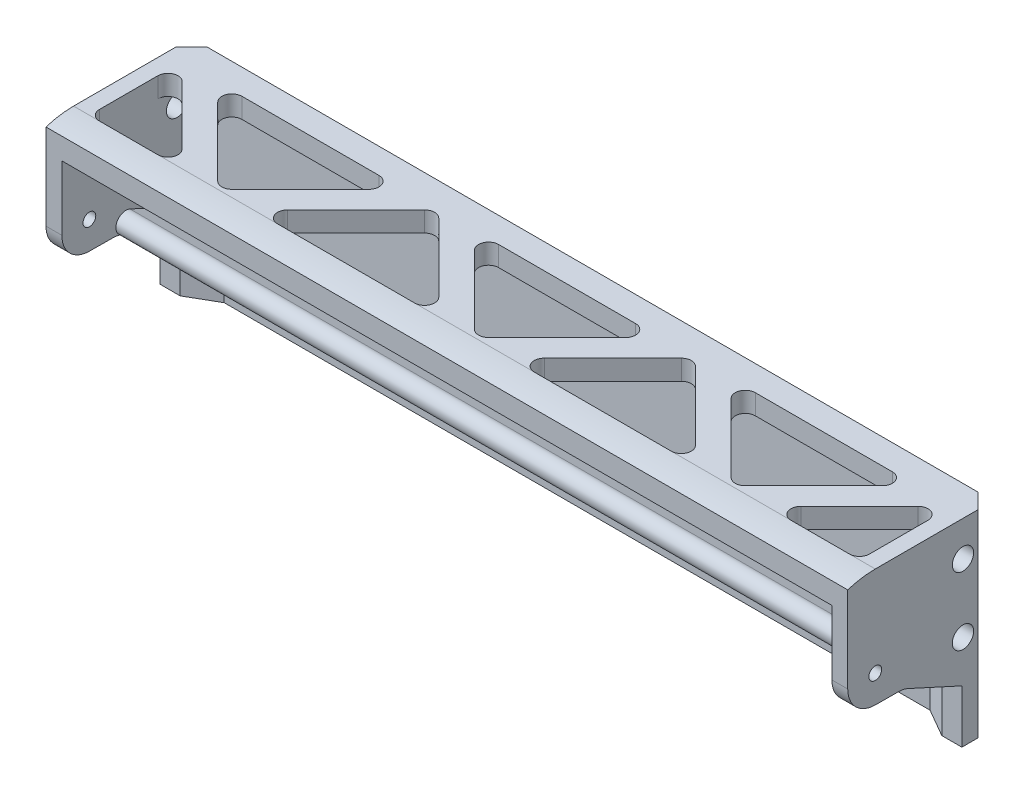
SolidWorks part; units mm, degrees
material "PET"
ref_plane "Front Plane" through (0, 0, 0) normal (0, 0, 1) x (1, 0, 0)
ref_plane "Top Plane" through (0, 0, 0) normal (0, 1, 0) x (1, 0, 0)
ref_plane "Right Plane" through (0, 0, 0) normal (1, 0, 0) x (0, 0, -1)
sketch "Sketch1" plane through (0, 0, 0) normal (1, 0, 0) x (0, 0, -1)
  line L3 (-34.036, 0) -> (42.164, 0) construction
  line L4 (-34.036, 0) -> (-34.036, 28.956) construction
  line L5 (-34.036, 28.956) -> (42.164, 28.956) construction
  line L11 (19.8576, 39.1492) -> (42.164, 28.956)
  line L12 (42.164, 28.956) -> (42.164, 0) construction
  line L13 (42.164, 28.956) -> (42.164, 14.4653)
  line L14 (46.99, 14.4653) -> (46.99, 77.089)
  line L15 (42.164, 14.4653) -> (46.99, 14.4653)
  line L16 (0.889, 48.514) -> (0.889, 75.7224)
  line L17 (9.5529, 39.783) -> (17.2674, 39.7235)
  line L18 (9.6202, 77.089) -> (46.99, 77.089)
  line L20 (37.4015, 44.4881) -> (69.4015, 44.4881) construction
  line L21 (22.4969, 44.9248) -> (42.164, 35.9376) construction
  circle A0 centre (9.6202, 48.514) radius 2.0193
  arc A2 (0.889, 48.514) -> (9.5529, 39.783) centre (9.6202, 48.514) ccw
  circle A7 centre (21.1772, 42.037) radius 3.175 construction
  arc A8 (19.8576, 39.1492) -> (17.2674, 39.7235) centre (17.2184, 33.3737) ccw
  arc A9 (9.6202, 77.089) -> (0.889, 75.7224) centre (9.6202, 48.514) ccw
  circle A12 centre (37.4015, 65.9765) radius 3.3782
  circle A14 centre (37.4015, 44.4881) radius 3.3782
  point P9 (0.889, 48.514)
  dimension "D2" = 4.0386
  dimension "D5" = 0.889
  dimension "D6" = 17.4625
  dimension "D8" = 6.35
  dimension "D13" = 6.35
  dimension "D14" = 28.575
  dimension "D15" = 9.5885
  dimension "D20" = 6.7564
  dimension "D19" = 11.1125
  dimension "D3" = 42.037
  dimension "D4" = 48.514
  dimension "D7" = 11.557
  dimension "D9" = 28.956
  dimension "D10" = 76.2
  dimension "D11" = 41.275
  dimension "D12" = 14.4653
  dimension "D16" = 4.826
  dimension "D17" = 5.7976
  dimension "D18" = 44.4881
  dimension "D21" = 32
  dimension "D22" = 36.5125
  dimension "D23" = 21.4884
extrude "Boss-Extrude1" add sketch "Sketch1" against normal blind 5.017 contours A2 A0 A7 | L13 L15 L14 A2 region at (0, 55.1501, -25.809)
sketch "Sketch2" plane through (0, 0, 0) normal (1, 0, 0) x (0, 0, -1)
  line L0 (22.4969, 44.9248) -> (42.164, 35.9376)
  line L1 (42.164, 35.9376) -> (42.164, 70.739)
  line L2 (42.164, 70.739) -> (40.64, 70.739)
  line L3 (40.64, 70.739) -> (9.6202, 70.739)
  line L4 (46.99, 14.4653) -> (46.99, 77.089)
  line L5 (46.99, 77.089) -> (9.6202, 77.089)
  line L6 (46.99, 14.4653) -> (46.99, 77.089)
  line L7 (46.99, 77.089) -> (9.6202, 77.089)
  line L8 (0.889, 48.514) -> (0.889, 75.7224) construction
  line L9 (0.889, 68.9521) -> (0.889, 75.7224)
  line L10 (46.99, 14.4653) -> (42.164, 14.4653)
  line L11 (42.164, 14.4653) -> (42.164, 28.956)
  line L12 (19.8576, 39.1492) -> (42.164, 28.956)
  line L13 (40.64, 14.4653) -> (40.64, 70.739) construction
  circle A0 centre (21.1772, 42.037) radius 3.175
  arc A1 (9.6202, 70.739) -> (2.8293, 69.6761) centre (9.6202, 48.514) ccw
  arc A2 (9.6202, 77.089) -> (0.889, 75.7224) centre (9.6202, 48.514) ccw
  arc A3 (9.6202, 77.089) -> (0.889, 75.7224) centre (9.6202, 48.514) ccw
  arc A4 (2.8293, 69.6761) -> (0.889, 68.9521) centre (9.6202, 48.514) ccw
  circle A5 centre (21.1772, 42.037) radius 3.175 construction
  line M17 (46.99, 77.089) -> (9.6202, 77.089)
  arc M18 (9.6202, 77.089) -> (0.889, 75.7224) centre (9.6202, 48.514) ccw
  line M19 (0.889, 75.7224) -> (0.889, 48.514)
  line M23 (19.8576, 39.1492) -> (42.164, 28.956)
  line M24 (42.164, 28.956) -> (42.164, 14.4653)
  line M25 (42.164, 14.4653) -> (46.99, 14.4653)
  line M26 (46.99, 14.4653) -> (46.99, 77.089)
  dimension "D1" = 0
  dimension "D2" = 6.35
extrude "Boss-Extrude2" add sketch "Sketch2" along normal blind 121.983 contours A4 A1 L3 M24 M25 M26 M17 M18 M19 | A0 L0 M23 | A0 region at (0, 39.7239, -32.0072) region at (0, 42.037, -21.1772)
sketch "Sketch5" plane through (0, 14.4653, 0) normal (0, -1, 0) x (1, 0, 0)
  line L0 (18.533, -46.99) -> (1.333, -37.0596)
  line L1 (-5.017, -46.99) -> (121.983, -46.99) construction
  line L2 (-5.017, -37.0596) -> (-5.017, -46.99)
  line L3 (-5.017, -46.99) -> (18.533, -46.99)
  line L4 (5.833, -46.99) -> (-5.017, -40.7257)
  line L5 (-5.017, -37.0596) -> (1.333, -37.0596)
  line M6 (121.983, -42.164) -> (-5.017, -42.164)
  dimension "D1" = 30
  dimension "D2" = 23.55
  dimension "D3" = 6.35
  dimension "D4" = 9.9304
extrude "Boss-Extrude3" add sketch "Sketch5" against normal up to surface (14.4907 mm away) contours L5 L2 L4 L0 M6 | L4 L2 M6 region at (0.8343, 14.4653, -39.9029) region at (-4.1866, 14.4653, -41.6846) up to face at (46.7864, 35.0719, -28.7802)
mirror "Mirror1" about plane through (121.983, 0, 0) normal (1, 0, 0) of bodies 106 103
sketch "Sketch4" plane through (0, 0, -46.99) normal (0, 0, -1) x (-1, 0, 0)
  line L0 (-121.983, -112.5347) -> (-280.2948, 45.7772) construction
  line L1 (-121.983, -112.5347) -> (36.3289, 45.7772) construction
  line L2 (-280.2948, 45.7772) -> (-121.983, 204.089) construction
  line L3 (36.3289, 45.7772) -> (-121.983, 204.089) construction
  line L4 (-121.983, -112.5347) -> (-121.983, 204.089) construction
  line L5 (-280.2948, 45.7772) -> (36.3289, 45.7772) construction
  point P1 (-121.983, 45.7772)
  dimension "D1" = 223.8868
chamfer "Chamfer1" distance 4.826 angle 45 2 edges at (248.983, 45.7771, -46.99) (-5.017, 45.7771, -46.99)
fillet "Fillet1" radius 3.175 2 edges at (121.983, 35.9376, -42.164) (121.983, 70.739, -42.164)
sketch "Sketch9" plane through (0, 70.739, 0) normal (0, -1, 0) x (1, 0, 0)
  line L0 (0, -9.6203) -> (0, -38.989)
  line L1 (0, -38.989) -> (29.3687, -9.6203)
  line L2 (243.966, -9.6203) -> (0, -9.6203) construction
  line L3 (29.3687, -9.6203) -> (0, -9.6203)
  line L4 (11.2922, -38.989) -> (40.661, -9.6203)
  line L5 (0, -38.989) -> (243.966, -38.989) construction
  line L6 (40.661, -9.6203) -> (70.0297, -38.989)
  line L7 (70.0297, -38.989) -> (11.2922, -38.989)
  line L8 (51.9532, -9.6203) -> (81.322, -38.989)
  line L9 (81.322, -38.989) -> (110.6907, -9.6203)
  line L10 (110.6907, -9.6203) -> (51.9532, -9.6203)
  line L11 (29.3687, -9.6203) -> (40.661, -9.6203) construction
  line L13 (40.661, -9.6203) -> (51.9532, -9.6203) construction
  line L14 (110.6907, -9.6203) -> (121.983, -9.6203) construction
  line L15 (29.3687, -9.6203) -> (35.0149, -15.2664) construction
  line L16 (121.983, -9.6203) -> (92.6142, -38.989)
  line L17 (92.6142, -38.989) -> (121.983, -38.989)
  line L18 (121.983, -38.989) -> (121.983, -9.6203)
  point P15 (121.983, -9.6203)
extrude "Cut-Extrude1" cut sketch "Sketch9" against normal through all
mirror "Mirror2" about plane through (121.983, 77.089, -38.989) normal (1, 0, 0) of "Cut-Extrude1"
fillet "Fillet2" radius 3.175 21 edges at (0, 73.914, -38.989) (0, 73.914, -9.6202) (11.2922, 73.914, -38.989) (70.0297, 73.914, -38.989) (40.661, 73.914, -9.6202) (81.322, 73.914, -38.989) (51.9532, 73.914, -9.6202) (110.6907, 73.914, -9.6202) (92.6142, 73.914, -38.989) (151.3517, 73.914, -38.989) (121.983, 73.914, -9.6202) (162.644, 73.914, -38.989) (133.2752, 73.914, -9.6202) (192.0127, 73.914, -9.6202) (173.9362, 73.914, -38.989) (203.305, 73.914, -9.6202) (232.6737, 73.914, -38.989) (243.966, 73.914, -38.989) (214.5972, 73.914, -9.6202) (243.966, 73.914, -9.6202) (29.3687, 73.914, -9.6202)
